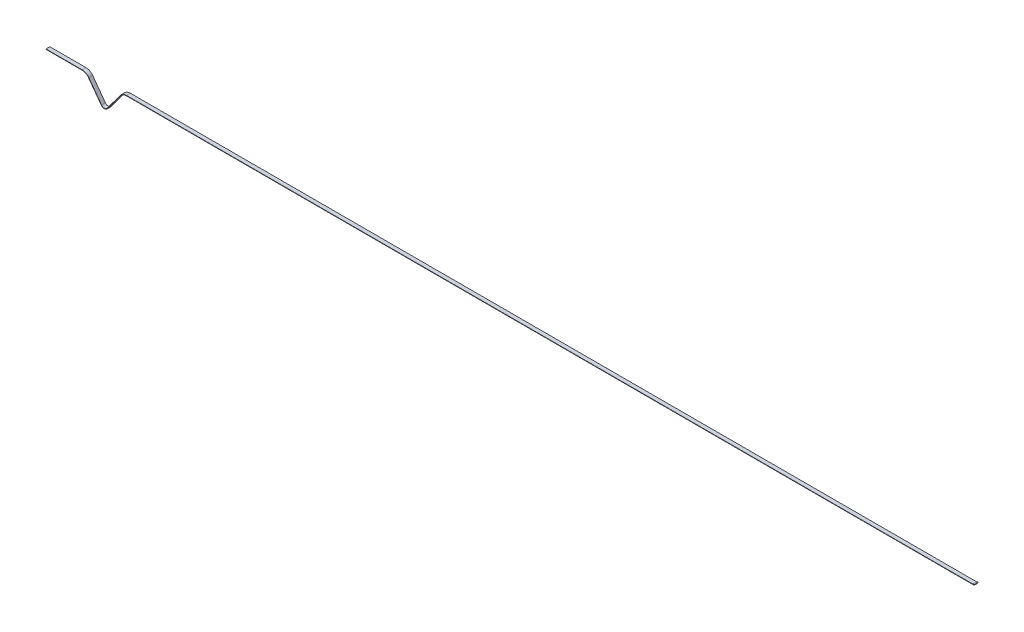
SolidWorks part; units mm, degrees
ref_plane "Front Plane" through (0, 0, 0) normal (0, 0, 1) x (1, 0, 0)
ref_plane "Top Plane" through (0, 0, 0) normal (0, 1, 0) x (1, 0, 0)
ref_plane "Right Plane" through (0, 0, 0) normal (1, 0, 0) x (0, 0, -1)
sketch "Sketch1" plane through (0, 0, 0) normal (1, 0, 0) x (0, 0, -1)
  line L1 (0, 0) -> (6, 0)
  line L2 (0, 0) -> (0, 0.63)
  line L3 (0, 0.63) -> (6, 0.63)
  line L4 (6, 0) -> (6, 0.63)
  dimension "D1" = 0.63
  dimension "D2" = 6
sketch "Sketch2" plane through (0, 0, 0) normal (0, 0, 1) x (1, 0, 0)
  line L0 (0, 0) -> (-1322.1665, 0)
  line L1 (-1331.7992, -4.8779) -> (-1351.8113, -32.1359)
  line L2 (-1361.6617, -32.1359) -> (-1381.6738, -4.8779)
  line L3 (-1391.3065, 0) -> (-1447.8, 0)
  arc A0 (-1322.1665, 0) -> (-1331.7992, -4.8779) centre (-1322.1665, -11.95) ccw
  arc A1 (-1351.8113, -32.1359) -> (-1361.6617, -32.1359) centre (-1356.7365, -28.52) cw
  arc A2 (-1381.6738, -4.8779) -> (-1391.3065, 0) centre (-1391.3065, -11.95) ccw
  circle A3 centre (-1356.7365, -28.52) radius 8 construction
  circle A4 centre (-1322.1665, -11.95) radius 11.95 construction
  circle A5 centre (-1391.3065, -11.95) radius 11.95 construction
  dimension "D1" = 6.11
  dimension "D4" = 1447.8
sweep "Sweep1" add profiles "Sketch1" path "Sketch2"
sketch "Sketch3" plane through (0, 0, 0) normal (0, 0, 1) x (1, 0, 0)
  line L0 (0, 0.63) -> (-1322.1665, 0.63) construction
  line L1 (-1.5, 0.63) -> (-1.5, 0)
  line L2 (0, 0) -> (-1322.1665, 0) construction
  line L3 (-1.5, 0) -> (0, 0)
  line L4 (0, 0) -> (0, 0.63)
  arc A1 (0, 0.63) -> (-1.5, 0.63) centre (-0.75, 0.63) ccw
  dimension "D1" = 0.75
extrude "Boss-Extrude1" add sketch "Sketch3" against normal through all
pattern_curve "CrvPattern1" [suppressed] of bodies 102 driven by "Sketch2" parameters "D1"=2000, "D3"=2, "D2"=1, "D4"=10
